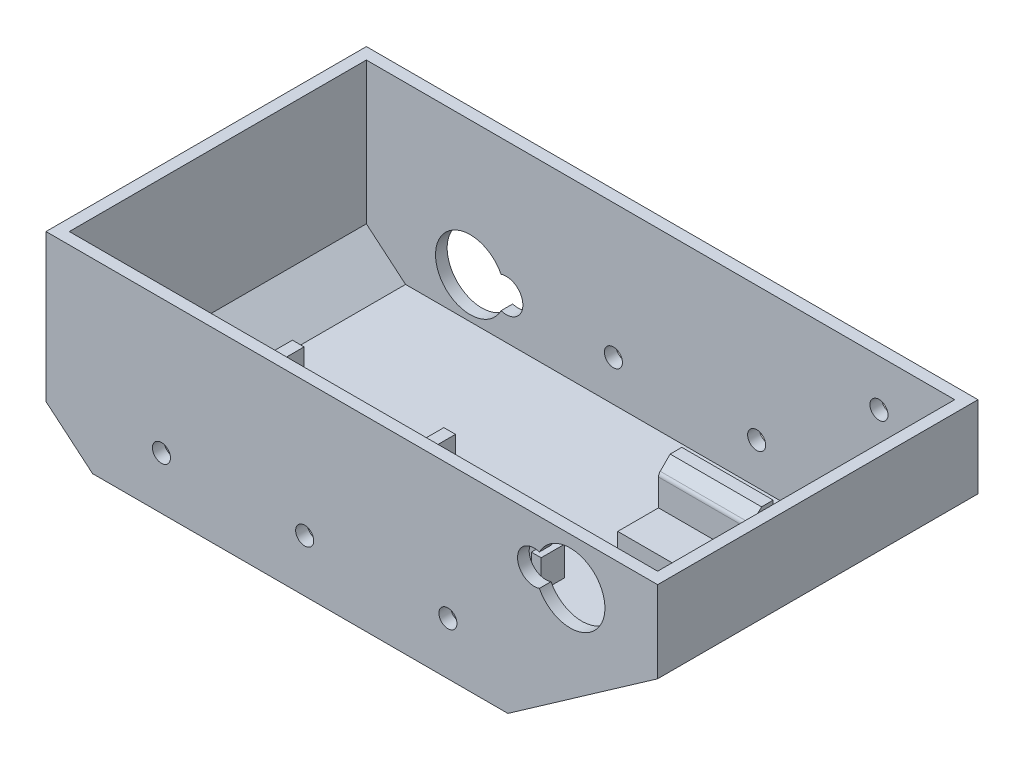
SolidWorks part; units mm, degrees
ref_plane "Ebene vorne" through (0, 0, 0) normal (0, 0, 1) x (1, 0, 0)
ref_plane "Ebene oben" through (0, 0, 0) normal (0, 1, 0) x (1, 0, 0)
ref_plane "Ebene rechts" through (0, 0, 0) normal (1, 0, 0) x (0, 0, -1)
sketch "Skizze1" plane through (0, 0, 0) normal (0, 1, 0) x (1, 0, 0)
  line L0 (0, 0) -> (105, 0)
  line L1 (-17.6, 0) -> (17.6, 0) construction
  line L2 (105, 0) -> (105, 55)
  line L3 (105, 55) -> (0, 55)
  line L4 (0, -17.6) -> (0, 17.6) construction
  line L5 (0, 55) -> (0, 0)
  dimension "D1" = 105
  dimension "D2" = 55
extrude "Aufsatz-Linear austragen1" add sketch "Skizze1" along normal blind 32
ref_plane "Ebene_Mitte" through (0, 0, -27.5) normal (0, 0, 1) x (1, 0, 0)
chamfer "Fase_Vorne" distance 18 angle 55 1 edges at (105, 0, -27.5) first distance on face at (105, 16, -27.5)
chamfer "Fase_Hinten " distance 8 angle 40 1 edges at (0, 0, -27.5) first distance on face at (39.6467, 0, -27.5)
shell "Ausschnitt_Innen" thickness 2 removed face at (52.5, 32, -27.5)
sketch "Skizze3" plane through (0, 0, 0) normal (0, 0, 1) x (1, 0, 0)
  line L0 (30.4204, 0) -> (-30.4204, 0) construction
  line L1 (-17.2504, 9) -> (19.82, 9) construction
  line L2 (19.82, 9) -> (44.41, 9) construction
  line L3 (105, 32) -> (105, 18) construction
  line L4 (44.41, 9) -> (69, 9) construction
  line L5 (69, 9) -> (93.2503, 9) construction
  circle A0 centre (19.82, 9) radius 1.55
  circle A1 centre (90, 24) radius 1.55
  circle A2 centre (44.41, 9) radius 1.55
  circle A3 centre (69, 9) radius 1.55
  dimension "D1" = 3.1
  dimension "D5" = 15
  dimension "D6" = 21
  dimension "D2" = 9
  dimension "D4" = 15
  dimension "D7" = 49.18
extrude "Bohrungen_Antrieb" cut sketch "Skizze3" against normal up to surface (2 mm away) up to face at (49.5651, 15.7811, -2)
mirror "Bohrung_gespiegelt_Links" about plane through (0, 0, -27.5) normal (0, 0, 1) of "Bohrungen_Antrieb"
sketch "Skizze4" plane through (0, 0, 0) normal (0, 0, 1) x (1, 0, 0)
  line L0 (90, 24) -> (107.6017, 24) construction
  line L1 (90, 24) -> (78.7402, 24) construction
  arc A0 (84.7, 21.2958) -> (84.7, 26.7042) centre (90, 24) ccw
  arc A1 (84.7, 26.7042) -> (84.7, 21.2958) centre (83.8, 24) ccw
  dimension "D1" = 11.9
  dimension "D2" = 5.7
  dimension "D3" = 6.2
extrude "Aussparung_Servo_Vorne" cut sketch "Skizze4" against normal up to surface (2 mm away) up to face at (18.27, 9, -2)
sketch "Skizze5" plane through (0, 0, -55) normal (0, 0, -1) x (-1, 0, 0)
  line L0 (-19.82, 9) -> (2.5158, 9) construction
  line L1 (-19.82, 9) -> (-31.1075, 9) construction
  arc A0 (-25.12, 6.2958) -> (-25.12, 11.7042) centre (-19.82, 9) ccw
  arc A2 (-25.12, 11.7042) -> (-25.12, 6.2958) centre (-26.02, 9) ccw
  dimension "D1" = 5.7
  dimension "D2" = 11.9
  dimension "D3" = 6.2
extrude "Aussparung_Servo_Hinten" cut sketch "Skizze5" against normal up to surface (2 mm away) up to face at (21.37, 9, -53)
sketch "Skizze8" plane through (0, 0, -27.5) normal (0, 0, 1) x (1, 0, 0)
  line L1 (78.6627, 2) -> (103, 19.0411) construction
  line L3 (78.6523, 23.9927) -> (78.6523, 1.9927)
  line L6 (78.6523, 23.9927) -> (94.345, 23.9927)
  line L7 (94.345, 23.9927) -> (94.345, 12.9808)
  line L8 (94.345, 12.9808) -> (78.6523, 1.9927)
  dimension "D1" = 22
extrude "Aufsatz_Servobegrenzung_unten" add sketch "Skizze8" along normal blind 8 and the other way blind 3 separate body
sketch "Skizze12" plane through (0, 23.9927, 0) normal (0, 1, 0) x (1, 0, 0)
  line L0 (94.345, 19.5) -> (94.345, 26.5)
  line L1 (94.345, 30.5) -> (94.345, 19.5) construction
  line L2 (94.345, 26.5) -> (78.6523, 26.5)
  line L3 (78.6523, 30.5) -> (78.6523, 19.5) construction
  line L4 (78.6523, 26.5) -> (78.6523, 19.5)
  line L5 (78.6523, 19.5) -> (94.345, 19.5)
  dimension "D1" = 7
extrude "Ausschnitt_Servomontage" cut sketch "Skizze12" against normal blind 7
chamfer "Servomontage" distance 2 angle 45 1 edges at (86.4986, 23.9927, -26.5)
fillet "Servomontage_2" radius 1 1 edges at (86.4986, 21.9927, -26.5)
sketch "Skizze15" plane through (0, 2, 0) normal (0, 1, 0) x (1, 0, 0)
  line L0 (39.3, 31) -> (39.3, 26)
  line L1 (39.3, 26) -> (34.3, 26)
  line L2 (34.3, 26) -> (34.3, 28)
  line L3 (34.3, 28) -> (37.3, 28)
  line L4 (37.3, 28) -> (37.3, 31)
  line L5 (37.3, 31) -> (39.3, 31)
  line L6 (16.3, 26) -> (11.3, 26)
  line L7 (11.3, 26) -> (11.3, 31)
  line L8 (11.3, 31) -> (13.3, 31)
  line L9 (13.3, 31) -> (13.3, 28)
  line L10 (13.3, 28) -> (16.3, 28)
  line L11 (16.3, 28) -> (16.3, 26)
  line L13 (78.6627, 53) -> (8.7279, 53) construction
  line L17 (2, 53) -> (2, 2) construction
  dimension "D1" = 5
  dimension "D2" = 5
  dimension "D3" = 2
  dimension "D4" = 2
  dimension "D5" = 5
  dimension "D6" = 2
  dimension "D7" = 5
  dimension "D8" = 2
  dimension "D9" = 25
  dimension "D10" = 24
  dimension "D11" = 11.3
extrude "Halterung_Servo_hinten " add sketch "Skizze15" along normal blind 4 from surface starting at face at (43.6953, 2, -27.5)
chamfer "Montagehilfe hinten" distance 1 angle 45 1 edges at (35.8, 6, -28)
chamfer "Montagehilfe hinten _2 " distance 1 angle 45 1 edges at (14.8, 6, -28)
sketch "Skizze16" plane through (0, 2, 0) normal (0, 1, 0) x (1, 0, 0)
  line L0 (66, 23) -> (12, 23)
  line L1 (12, 23) -> (12, 5)
  line L2 (12, 5) -> (66, 5)
  line L3 (66, 5) -> (66, 23)
  line L4 (2, 53) -> (2, 2) construction
  line L5 (8.7279, 2) -> (78.6627, 2) construction
  dimension "D1" = 18
  dimension "D2" = 54
  dimension "D3" = 10
  dimension "D4" = 3
extrude "Aufsatz-Linear austragen8" add sketch "Skizze16" along normal blind 5
sketch "Skizze19" plane through (0, 7, 0) normal (0, 1, 0) x (1, 0, 0)
  line L0 (61, 24.8356) -> (61, 2.952)
  line L1 (61, 2.952) -> (17, 2.952)
  line L2 (17, 2.952) -> (17, 24.8356)
  line L3 (17, 24.8356) -> (61, 24.8356)
  line L4 (66, 5) -> (66, 23) construction
  line L5 (12, 23) -> (12, 5) construction
  dimension "D1" = 5
  dimension "D2" = 5
extrude "Schnitt-Linear austragen6" cut sketch "Skizze19" against normal up to surface (5 mm away) up to face at (13.6333, 2, -28.3333)
sketch "Skizze20" plane through (0, 7, 0) normal (0, 1, 0) x (1, 0, 0)
  line L0 (64.3202, 21) -> (60.3202, 21)
  line L1 (60.3202, 21) -> (60.3202, 7)
  line L2 (60.3202, 7) -> (64.3202, 7)
  line L3 (64.3202, 7) -> (64.3202, 9)
  line L4 (64.3202, 9) -> (68.5868, 9)
  line L5 (68.5868, 9) -> (68.5868, 19)
  line L6 (68.5868, 19) -> (64.3202, 19)
  line L7 (64.3202, 19) -> (64.3202, 21)
  line L8 (66, 23) -> (61, 23) construction
  line L9 (61, 5) -> (66, 5) construction
  dimension "D1" = 2
  dimension "D2" = 2
  dimension "D3" = 4
  dimension "D4" = 4
  dimension "D5" = 2
  dimension "D6" = 2
extrude "Schnitt-Linear austragen7" cut sketch "Skizze20" against normal up to surface (5 mm away) up to face at (63.5, 2, -14)
sketch "Skizze21" plane through (0, 7, 0) normal (0, 1, 0) x (1, 0, 0)
  line L0 (18.9503, 21) -> (14, 21)
  line L1 (14, 21) -> (14, 19)
  line L2 (14, 19) -> (10.6477, 19)
  line L3 (10.6477, 19) -> (10.6477, 9)
  line L4 (10.6477, 9) -> (14, 9)
  line L5 (14, 9) -> (14, 7)
  line L6 (14, 7) -> (18.9503, 7)
  line L7 (18.9503, 7) -> (18.9503, 21)
  line L8 (17, 23) -> (12, 23) construction
  line L11 (12, 23) -> (12, 5) construction
  line L12 (12, 5) -> (17, 5) construction
  dimension "D1" = 2
  dimension "D2" = 2
  dimension "D3" = 2
  dimension "D4" = 2
  dimension "D5" = 2
  dimension "D6" = 2
extrude "Schnitt-Linear austragen8" cut sketch "Skizze21" against normal up to surface (5 mm away) up to face at (63.7734, 2, -21)
